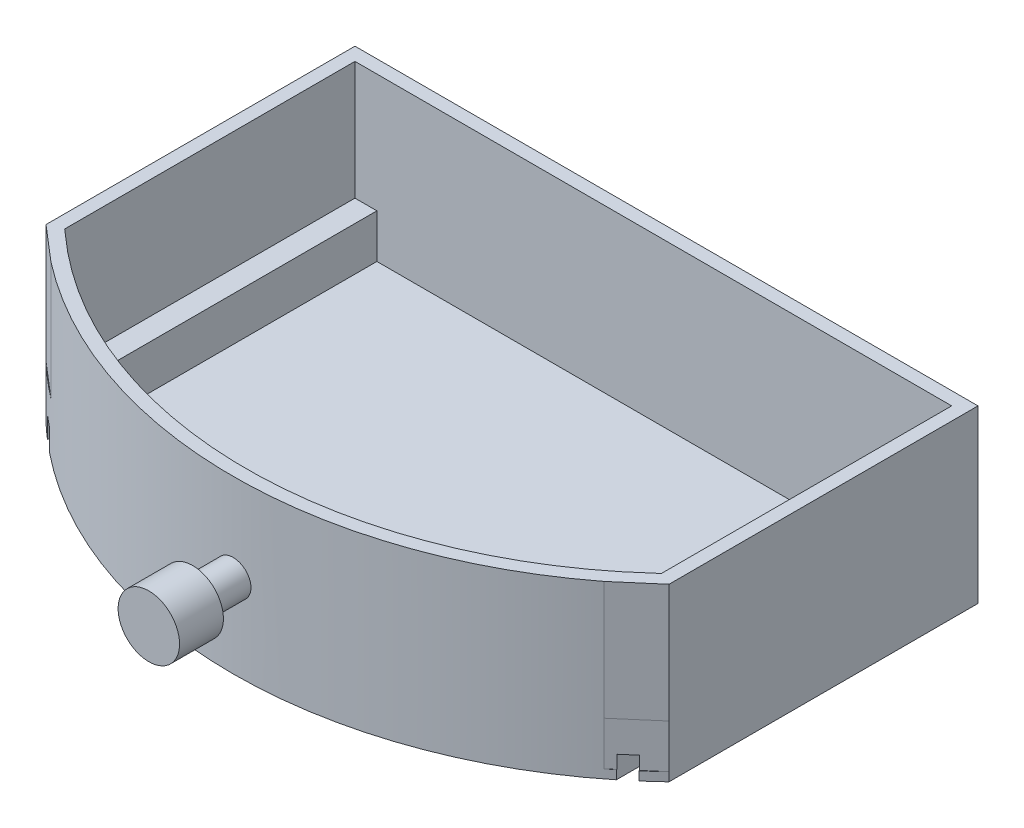
SolidWorks part; units mm, degrees
ref_plane "前视基准面" through (0, 0, 0) normal (0, 0, 1) x (1, 0, 0)
ref_plane "上视基准面" through (0, 0, 0) normal (0, 1, 0) x (1, 0, 0)
ref_plane "右视基准面" through (0, 0, 0) normal (1, 0, 0) x (0, 0, -1)
other "Configuration Table"
sketch "草图1" plane through (0, 0, 0) normal (0, 1, 0) x (1, 0, 0)
  line L0 (0, 0) -> (0, -70.42)
  line L1 (0, 0) -> (142, 0)
  line L3 (0, -70.42) -> (142, -70.42) construction
  line L4 (142, 0) -> (142, -70.42)
  circle A0 centre (71, 4.199) radius 103 construction
  arc A1 (0, -70.42) -> (142, -70.42) centre (71, 4.199) ccw
  dimension "D2" = 206
  dimension "D1" = 142
  dimension "D3" = 70.42
extrude "凸台-拉伸1" add sketch "草图1" along normal blind 2
sketch "草图2" plane through (0, 2, 0) normal (0, 1, 0) x (1, 0, 0)
  line L0 (8, -77.2872) -> (134, -77.2872) construction
  line L1 (8, 0) -> (8, -77.2872)
  line L2 (142, 0) -> (0, 0) construction
  line L3 (8, 0) -> (0, 0)
  line L4 (0, 0) -> (0, -70.42)
  line L5 (134, -77.2872) -> (134, 0)
  line L6 (134, 0) -> (142, 0)
  line L7 (142, 0) -> (142, -70.42)
  line L8 (142, -70.42) -> (134, -77.2872)
  arc A0 (0, -70.42) -> (142, -70.42) centre (71, 4.199) ccw construction
  arc A2 (0, -70.42) -> (8, -77.2872) centre (71, 4.199) ccw
  arc A3 (142, -70.42) -> (134, -77.2872) centre (71, 4.199) cw
  dimension "D1" = 126
extrude "凸台-拉伸2" add sketch "草图2" along normal blind 10 contours L1 A2 L4 L3 | L8 L5 L6 L7
sketch "草图3" plane through (0, 0, 0) normal (0, -1, 0) x (1, 0, 0)
  line L0 (6, 0) -> (136, 0) construction
  line L1 (142, 0) -> (0, 0) construction
  line L2 (142, 70.42) -> (142, 0) construction
  line L3 (3.6, 0) -> (3.6, 73.687)
  line L4 (138.4, 0) -> (138.4, 73.687)
  line L5 (6.4, 0) -> (6.4, 76.0247)
  line L6 (135.6, 0) -> (135.6, 76.0247)
  line L7 (6.4, 76.0247) -> (3.6, 76.0247)
  line L8 (3.6, 76.0247) -> (3.6, 73.687)
  line L9 (135.6, 76.0247) -> (138.4, 76.0247)
  line L10 (138.4, 76.0247) -> (138.4, 73.687)
  line L11 (135.6, 0) -> (138.4, 0)
  line L12 (3.6, 0) -> (6.4, 0)
  arc A0 (142, 70.42) -> (0, 70.42) centre (71, -4.199) ccw construction
  dimension "D1" = 130
  dimension "D2" = 6
  dimension "D3" = 6
  dimension "D4" = 2.4
  dimension "D5" = 2.4
  dimension "D6" = 0.4
  dimension "D7" = 0.4
extrude "切除-拉伸1" cut sketch "草图3" against normal blind 5
sketch "草图4" plane through (0, 2, 0) normal (0, 1, 0) x (1, 0, 0)
  line L0 (134, -77.2872) -> (134, 0) construction
  line L1 (8, 0) -> (134, 0)
  line L2 (8, 0) -> (8, -3)
  line L3 (8, -3) -> (134, -3)
  line L4 (134, 0) -> (134, -3)
  line L5 (8, 0) -> (8, -77.2872) construction
  line L6 (8, -73.4605) -> (8, -77.2872)
  line L7 (134, -73.4605) -> (134.0369, -77.2586)
  circle A0 centre (71, 4.199) radius 103 construction
  arc A1 (8, -77.2872) -> (134.0369, -77.2586) centre (71, 4.199) ccw
  arc A2 (8, -73.4605) -> (134, -73.4605) centre (71, 4.199) ccw
  dimension "D2" = 100
  dimension "D1" = 3
extrude "凸台-拉伸4" add sketch "草图4" along normal blind 37
sketch "草图5" plane through (0, 12, 0) normal (0, 1, 0) x (1, 0, 0)
  line L0 (134, 0) -> (142, 0)
  line L1 (142, 0) -> (142, -70.42) construction
  line L2 (134, 0) -> (142, 0) construction
  line L3 (142, 0) -> (142, -70.42)
  line L4 (142, -70.42) -> (134.0369, -77.2586)
  line L5 (134.0369, -77.2586) -> (134, -73.4605)
  line L6 (134, -73.4605) -> (139, -69.1665)
  line L7 (139, -69.1665) -> (139, -3)
  line L8 (139, -3) -> (134, -3)
  line L9 (134, 0) -> (134, -3)
  line L10 (8, -3) -> (8, 0)
  line L11 (8, 0) -> (0, 0)
  line L12 (0, 0) -> (0, -70.42)
  line L13 (0, -70.42) -> (8, -77.2872)
  line L14 (8, -77.2872) -> (8, -73.4605)
  line L15 (8, -73.4605) -> (3, -69.1685)
  line L16 (3, -69.1685) -> (3, -3)
  line L17 (3, -3) -> (8, -3)
  dimension "D1" = 3
  dimension "D2" = 90
  dimension "D3" = 0
  dimension "D4" = 3
extrude "凸台-拉伸5" add sketch "草图5" along normal blind 27
sketch "草图6" plane through (0, 0, 3) normal (0, 0, 1) x (1, 0, 0)
  line L0 (134.0369, 39) -> (8, 39) construction
  circle A0 centre (71.0185, 19) radius 4
  dimension "D2" = 8
  dimension "D1" = 20
extrude "凸台-拉伸6" add sketch "草图6" along normal blind 110
sketch "草图7" plane through (0, 39, 0) normal (0, 1, 0) x (1, 0, 0)
  line L0 (75.0185, -95.7202) -> (75.0185, -3) construction
  line L1 (67.0185, -3) -> (75.0185, -3)
  line L2 (67.0185, -3) -> (67.0185, -95.7202)
  line L3 (67.0185, -95.7202) -> (75.0185, -95.7202)
  line L4 (75.0185, -3) -> (75.0185, -95.7202)
  arc A0 (8, -73.4605) -> (134, -73.4605) centre (71, 4.199) ccw construction
extrude "切除-拉伸2" cut sketch "草图7" against normal blind 25
sketch "草图8" plane through (0, 0, 113) normal (0, 0, 1) x (1, 0, 0)
  circle A0 centre (71.0185, 19) radius 7
  dimension "D1" = 14
extrude "凸台-拉伸7" add sketch "草图8" along normal blind 5 and the other way blind 5
